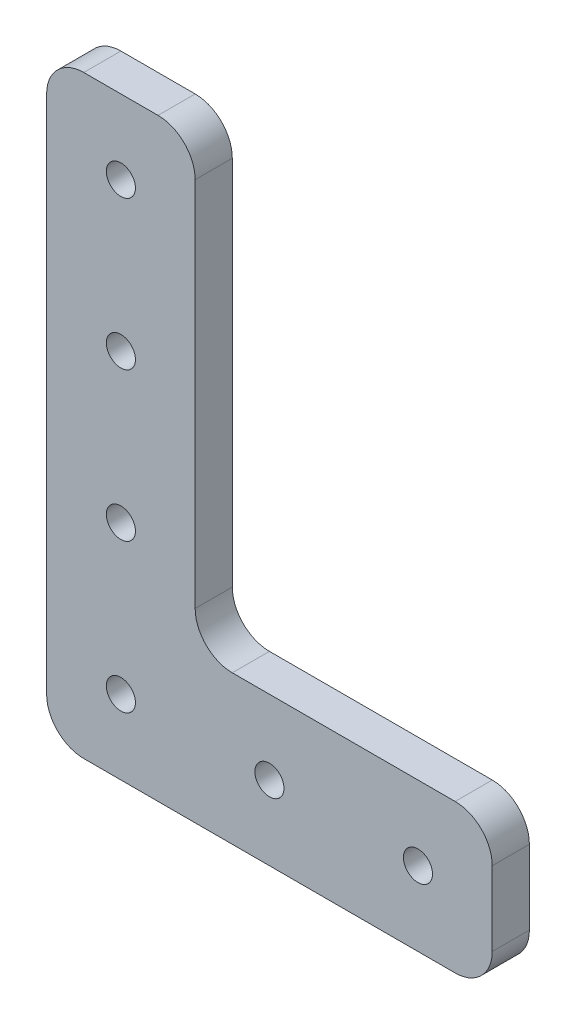
SolidWorks part; units mm, degrees
ref_plane "Front Plane" through (0, 0, 0) normal (0, 0, 1) x (1, 0, 0)
ref_plane "Top Plane" through (0, 0, 0) normal (0, 1, 0) x (1, 0, 0)
ref_plane "Right Plane" through (0, 0, 0) normal (1, 0, 0) x (0, 0, -1)
sketch "Sketch1" plane through (0, 0, 0) normal (0, 0, 1) x (1, 0, 0)
  line L0 (0, 0) -> (0, 101.6)
  line L1 (0, 101.6) -> (25.4, 101.6)
  line L2 (25.4, 101.6) -> (25.4, 25.4)
  line L3 (25.4, 25.4) -> (76.2, 25.4)
  line L4 (76.2, 25.4) -> (76.2, 0)
  line L5 (76.2, 0) -> (0, 0)
  circle A0 centre (12.7, 12.7) radius 2.4892
  circle A1 centre (38.1, 12.7) radius 2.4892
  circle A2 centre (63.5, 12.7) radius 2.4892
  circle A3 centre (38.1, 38.1) radius 2.4892 construction
  circle A4 centre (63.5, 38.1) radius 2.4892 construction
  circle A5 centre (38.1, 63.5) radius 2.4892 construction
  circle A6 centre (63.5, 63.5) radius 2.4892 construction
  circle A7 centre (38.1, 88.9) radius 2.4892 construction
  circle A8 centre (63.5, 88.9) radius 2.4892 construction
  circle A9 centre (12.7, 38.1) radius 2.4892
  circle A10 centre (12.7, 63.5) radius 2.4892
  circle A11 centre (12.7, 88.9) radius 2.4892
  dimension "D2" = 4.9784
  dimension "D1" = 25.4
  dimension "D3" = 12.7
  dimension "D4" = 12.7
  dimension "D7" = 25.4
  dimension "D8" = 25.4
  dimension "D9" = 12.7
  dimension "D10" = 12.7
  dimension "D5" = 3
  dimension "D6" = 4
extrude "Boss-Extrude1" add sketch "Sketch1" along normal blind 6.35
fillet "Fillet1" radius 6.35 6 edges at (0, 0, 3.175) (0, 101.6, 3.175) (25.4, 25.4, 3.175) (76.2, 25.4, 3.175) (76.2, 0, 3.175) (25.4, 101.6, 3.175)
